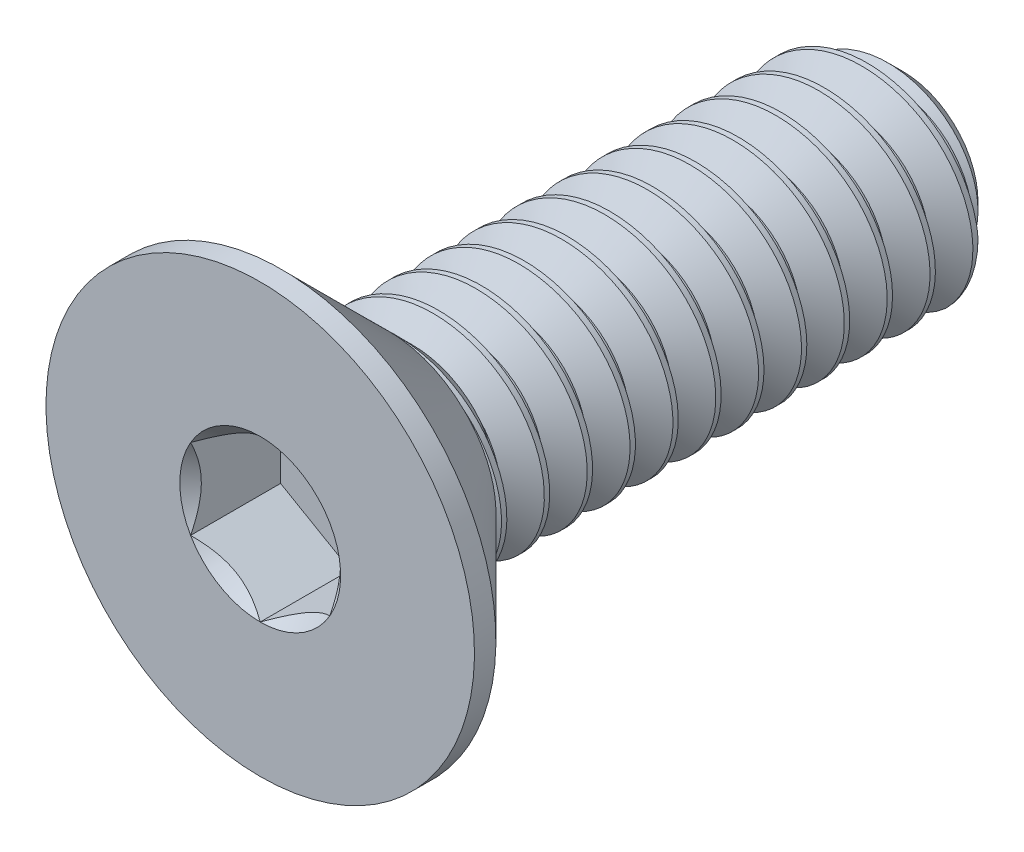
SolidWorks part; units mm, degrees
ref_plane "Front" through (0, 0, 0) normal (0, 0, 1) x (1, 0, 0)
ref_plane "Top" through (0, 0, 0) normal (0, 1, 0) x (1, 0, 0)
ref_plane "Right" through (0, 0, 0) normal (1, 0, 0) x (0, 0, -1)
sketch "Sketch1" plane through (0, 0, 0) normal (1, 0, 0) x (0, 0, -1)
  line L0 (0, 2) -> (0.2, 2) construction
  line L1 (0.2, 2) -> (1.2, 1) construction
  line L2 (0, 1) -> (6, 1)
  line L3 (6, 1) -> (6, 0)
  line L4 (6, 0) -> (0, 0)
  line L5 (0, 0) -> (0, 2) construction
  line L6 (0, 2) -> (0, -2) construction
  line L7 (6, 1) -> (6, -1) construction
  line L8 (0, -2) -> (0.2, -2) construction
  line L9 (0.2, -2) -> (1.2, -1) construction
  line L11 (0, 1) -> (0, 0)
  line L12 (1.2, 1) -> (1.2, 0) construction
  dimension "Head Ht" = 1.2
  dimension "Head Dia" = 4
  dimension "Dia" = 2
  dimension "Lg" = 6
  dimension "Head Angle" = 90
revolve "Revolve1" add sketch "Sketch1" angle 360 mid plane about L4
sketch "Sketch3" plane through (0, 0, -6) normal (0, 0, -1) x (-1, 0, 0)
  circle A0 centre (0, 0) radius 1
curve "Helix/Spiral1" pitch 0.4 height 6 radius 1 centre (0, 0, -6) axis (0, 0, 1) start towards (0, 1, 0)
sketch "Sketch2" plane through (0, 0, 0) normal (1, 0, 0) x (0, 0, -1)
  line L0 (6, 1) -> (6.35, 1)
  line L1 (6.35, 1) -> (6.2, 0.7402)
  line L2 (6.2, 0.7402) -> (6.15, 0.7402)
  line L3 (6.15, 0.7402) -> (6, 1)
  line L4 (6.075, 0.8701) -> (6.275, 0.8701) construction
  dimension "D1" = 60
  dimension "D2" = 0.05
  dimension "D3" = 0.2
chamfer "Chamfer1" distance 0.3 angle 45 1 edges at (0, 1, -6)
sweep "Cut-Sweep1" cut profiles "Sketch2" path "Helix/Spiral1" align with end faces yes
sketch "Sketch7" plane through (0, 0, 0) normal (1, 0, 0) x (0, 0, -1)
  line L0 (0, 2) -> (0.2, 2) construction
  line L1 (0.2, 2) -> (1.2, 1) construction
  line L2 (0, 2) -> (0.2, 2)
  line L3 (0.2, 2) -> (1.2, 1)
  line L4 (1.2, 1) -> (1.2, 0) construction
  line L5 (1.2, 1) -> (1.2, 0)
  line L7 (0, 0) -> (0, 2) construction
  line L8 (0, 0) -> (0, 2)
  line L9 (0, 0) -> (1.2, 0)
  line L10 (2.2, 0) -> (-2.2, 0) construction
revolve "Revolve2" add sketch "Sketch7" angle 360 mid plane about L9
ref_plane "Plane1" through (0, 0, -1.2) normal (0, 0, 1) x (1, 0, 0)
sketch "Sketch8" plane through (0, 0, -1.2) normal (0, 0, 1) x (1, 0, 0)
  circle A0 centre (0, 0) radius 1
extrude "Boss-Extrude1" add sketch "Sketch8" against normal through all draft 45
sketch "Sketch5" plane through (0, 0, 0) normal (0, 0, 1) x (1, 0, 0)
  line L1 (0.65, -0.3753) -> (0.65, 0.3753)
  line L2 (0.65, 0.3753) -> (0, 0.7506)
  line L3 (0, 0.7506) -> (-0.65, 0.3753)
  line L4 (-0.65, 0.3753) -> (-0.65, -0.3753)
  line L5 (-0.65, -0.3753) -> (0, -0.7506)
  line L6 (0, -0.7506) -> (0.65, -0.3753)
  circle A0 centre (0, 0) radius 0.65 construction
  dimension "Hex" = 1.3
extrude "Cut-Extrude2" cut sketch "Sketch5" against normal blind 0.84
sketch "Sketch6" plane through (0, 0, 0) normal (0, 0, 1) x (1, 0, 0)
  circle A0 centre (0, 0) radius 0.7506
extrude "Cut-Extrude3" cut sketch "Sketch6" against normal blind 0.84 draft 45
sketch "Sketch9" [suppressed] plane through (0, 0, -5.5) normal (0, 0, 1) x (1, 0, 0)
  circle A1 centre (0, 0) radius 5
  circle A2 centre (0, 0) radius 5
  point P0 (0, 5)
  dimension "D1" = 0
extrude "Boss-Extrude2" [suppressed] add sketch "Sketch9" against normal offset from surface (18.5 mm away) 26 up to face at (0, 0.7, -6)
fillet "Fillet1" [suppressed] radius 0.2
sketch "Sketch10" plane through (0, 0, 0) normal (1, 0, 0) x (0, 0, -1)
  line L0 (6, 1) -> (6, -1) construction
  point P0 (5.4, -1)
  dimension "D1" = 0.6
equation "\"D3@Helix/Spiral1\" = \"Lg@Sketch1\""
equation "\"D2@Sketch2\" = \"D4@Helix/Spiral1\" * .125"
equation "\"D3@Sketch2\" = \"D4@Helix/Spiral1\" * .5"
equation "\"D1@Chamfer1\" = \"D4@Helix/Spiral1\" * .75"
equation "\"D1@Cut-Extrude2\" = \"Head Ht@Sketch1\" * .7"
equation "\"D1@Sketch10\" = \"D4@Helix/Spiral1\" * 1.5"
equation "\"D1@Cut-Extrude3\" = \"D1@Cut-Extrude2\""
equation "\"D1@Fillet1\" = \"Dia@Sketch1\" * .1"
